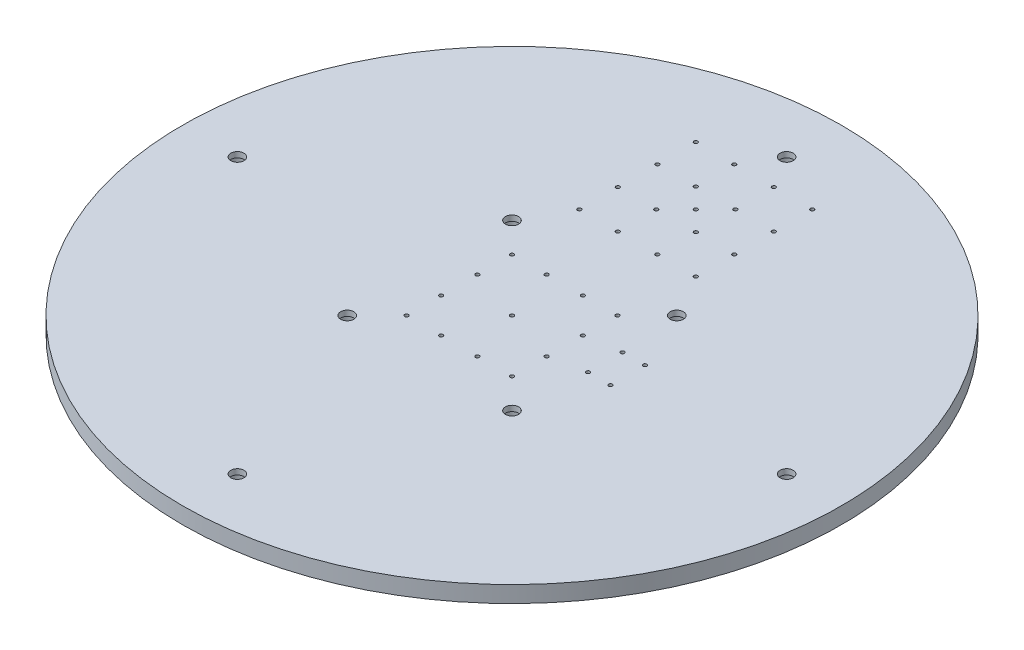
SolidWorks part; units mm, degrees
ref_plane "Front Plane" through (0, 0, 0) normal (0, 0, 1) x (1, 0, 0)
ref_plane "Top Plane" through (0, 0, 0) normal (0, 1, 0) x (1, 0, 0)
ref_plane "Right Plane" through (0, 0, 0) normal (1, 0, 0) x (0, 0, -1)
sketch "Sketch1" plane through (0, 0, 0) normal (0, 1, 0) x (1, 0, 0)
  circle A0 centre (0, 0) radius 300
  dimension "D1" = 600
extrude "Boss-Extrude1" add sketch "Sketch1" along normal blind 15
sketch "Extrusion Hole locations" plane through (0, 0, 0) normal (0, 1, 0) x (1, 0, 0)
  line L1 (75, -75) -> (-75, -75) construction
  line L2 (75, -75) -> (75, 75) construction
  line L3 (75, 75) -> (-75, 75) construction
  line L4 (-75, -75) -> (-75, 75) construction
  line L5 (75, -75) -> (-75, 75) construction
  line L6 (75, 75) -> (-75, -75) construction
  point P3 (0, 250)
  point P14 (250, 0)
  point P15 (0, -250)
  point P16 (-250, 0)
  point P105 (75, 75)
  point P108 (-75, 75)
  point P111 (-75, -75)
  point P114 (75, -75)
  point P116 (0, 0)
  dimension "D1" = 150
  dimension "D2" = 250
  dimension "D4" = 4
hole_wizard "CBORE for M10 SHCS1" positions "Extrusion Hole locations" profile "Sketch3" counterbore size "M10" standard "ANSI Metric" end condition through all
sketch "Sketch3" plane through (75, 0, 75) normal (1, 0, 0) x (0, 0, -1)
  line L0 (0, 0) -> (0, 15)
  line L1 (0, 15) -> (6, 15)
  line L3 (6, 15) -> (6, 10)
  line L4 (6, 10) -> (9, 10)
  line L5 (9, 10) -> (9, 0)
  line L7 (9, 0) -> (0, 0)
  line L11 (0, -6.35) -> (0, 107.95) construction
  dimension "Thru Hole Dia." = 12
  dimension "Thru Hole Depth" = 15
  dimension "C'Bore Dia." = 18
  dimension "C'Bore Depth" = 10
hole_wizard "CBORE for M3 SHCS1" positions "Sketch6" profile "Sketch7" counterbore size "M3" standard "ANSI Metric"
sketch "Sketch6" plane through (0, 0, 0) normal (0, -1, 0) x (-1, 0, 0)
  point P0 (0, 0)
  point P1 (0, 0)
  point P2 (-48, -48)
  point P3 (-48, -48)
  point P4 (16.5, -48)
  point P5 (-16.5, -48)
  point P6 (-16.5, -48)
  point P7 (48, -48)
  point P8 (48, -16.5)
  point P9 (48, 16.5)
  point P10 (48, 48)
  point P11 (16.5, 48)
  point P12 (-16.5, 48)
  point P13 (-48, 48)
  point P14 (0, 0)
  point P15 (0, 0)
  point P16 (-79.35, -10.1)
  point P17 (-99.7, -10.1)
  point P18 (-99.7, 21.3)
  point P19 (-79.35, 21.3)
  point P20 (-48, -16.5)
  point P21 (-48, 16.5)
sketch "Sketch7" plane through (0, 0, 0) normal (1, 0, 0) x (0, 0, -1)
  line L0 (0, 0) -> (0, 15)
  line L1 (0, 15) -> (1.7, 15)
  line L2 (1.7, 15) -> (1.7, 4)
  line L3 (1.7, 4) -> (3.25, 4)
  line L4 (3.25, 4) -> (3.25, 0)
  line L5 (3.25, 0) -> (0, 0)
  line L6 (0, -6.35) -> (0, 107.95) construction
  dimension "Thru Hole Dia." = 3.4
  dimension "Thru Hole Depth" = 15
  dimension "C'Bore Dia." = 6.5
  dimension "C'Bore Depth" = 4
hole_wizard "CBORE for M3 SHCS2" positions "Sketch8" profile "Sketch9" counterbore size "M3" standard "ANSI Metric"
sketch "Sketch8" plane through (0, 0, 0) normal (0, -1, 0) x (-1, 0, 0)
  point P0 (0, 167.3209)
  point P1 (0, 167.3209)
  point P2 (0, 167.3209)
  point P3 (53, 114.3209)
  point P4 (53, 149.3209)
  point P5 (53, 185.3209)
  point P6 (53, 220.3209)
  point P7 (18, 220.3209)
  point P8 (-18, 220.3209)
  point P9 (-53, 220.3209)
  point P10 (-53, 185.3209)
  point P11 (-53, 149.3209)
  point P12 (-53, 114.3209)
  point P13 (-18, 114.3209)
  point P14 (18, 114.3209)
  point P15 (18, 149.3209)
  point P16 (18, 185.3209)
  point P17 (-18, 149.3209)
  point P18 (-18, 185.3209)
sketch "Sketch9" plane through (0, 0, -167.3209) normal (1, 0, 0) x (0, 0, -1)
  line L0 (0, 0) -> (0, 15)
  line L1 (0, 15) -> (1.7, 15)
  line L2 (1.7, 15) -> (1.7, 4)
  line L3 (1.7, 4) -> (3.25, 4)
  line L4 (3.25, 4) -> (3.25, 0)
  line L5 (3.25, 0) -> (0, 0)
  line L6 (0, -6.35) -> (0, 107.95) construction
  dimension "Thru Hole Dia." = 3.4
  dimension "Thru Hole Depth" = 15
  dimension "C'Bore Dia." = 6.5
  dimension "C'Bore Depth" = 4
